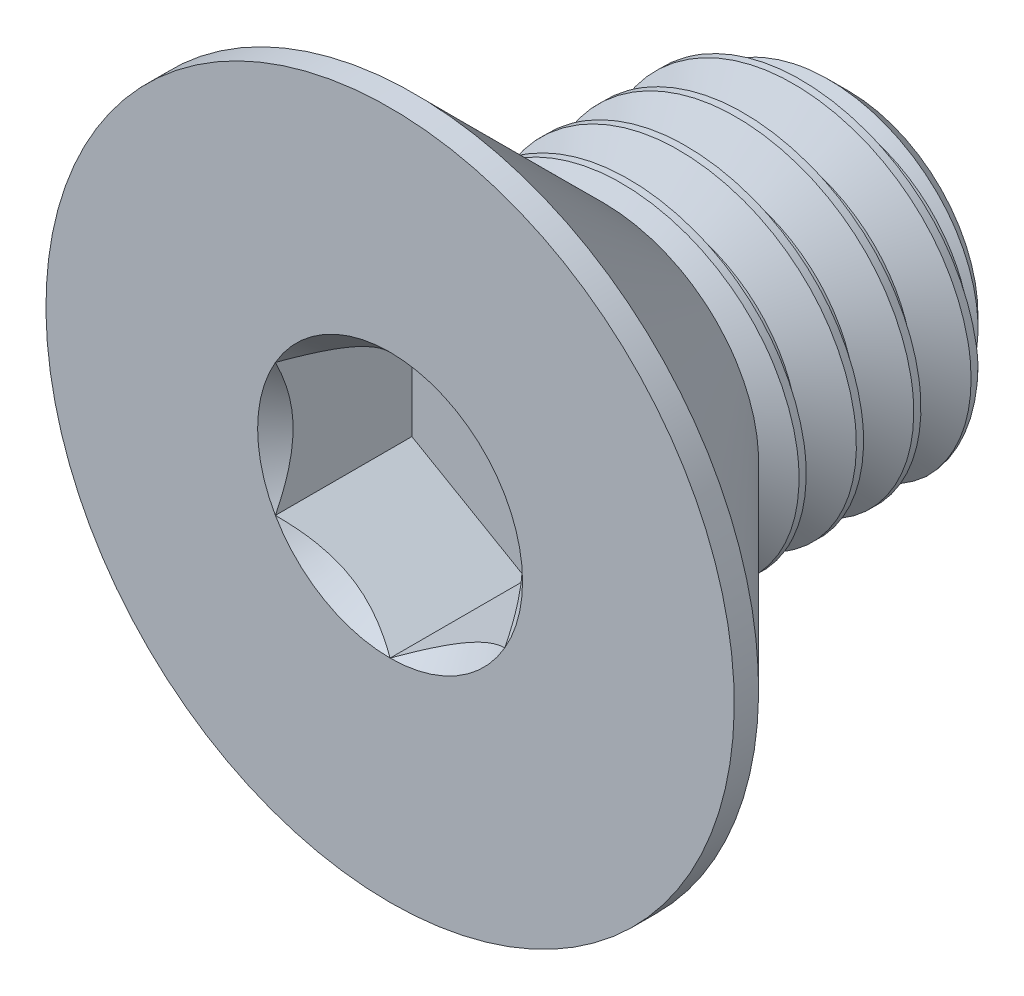
SolidWorks part; units mm, degrees
ref_plane "Front" through (0, 0, 0) normal (0, 0, 1) x (1, 0, 0)
ref_plane "Top" through (0, 0, 0) normal (0, 1, 0) x (1, 0, 0)
ref_plane "Right" through (0, 0, 0) normal (1, 0, 0) x (0, 0, -1)
sketch "Sketch1" plane through (0, 0, 0) normal (1, 0, 0) x (0, 0, -1)
  line L0 (0, 3) -> (0.2125, 3) construction
  line L1 (0.2125, 3) -> (1.7, 1.5125) construction
  line L2 (0, 1.5) -> (4, 1.5)
  line L3 (4, 1.5) -> (4, 0)
  line L4 (4, 0) -> (0, 0)
  line L5 (0, 0) -> (0, 3) construction
  line L6 (0, 3) -> (0, -3) construction
  line L7 (4, 1.5) -> (4, -1.5) construction
  line L8 (0, -3) -> (0.2125, -3) construction
  line L9 (0.2125, -3) -> (1.7, -1.5125) construction
  line L11 (0, 1.5) -> (0, 0)
  line L12 (1.7, 1.5125) -> (1.7, 0) construction
  line L13 (1.7, 1.5125) -> (1.4875, 1.5125) construction
  line L14 (1.4875, 1.5125) -> (1.275, 1.5125) construction
  line L15 (1.275, 1.5125) -> (1.0625, 1.5125) construction
  line L16 (1.0625, 1.5125) -> (0.85, 1.5125) construction
  line L17 (0.85, 1.5125) -> (0.6375, 1.5125) construction
  line L18 (0.6375, 1.5125) -> (0.425, 1.5125) construction
  line L19 (0.425, 1.5125) -> (0.2125, 1.5125) construction
  line L20 (0.2125, 1.5125) -> (0, 1.5125) construction
  line L21 (3.9688, 1.5541) -> (4.4688, 1.5541) construction
  line L22 (4.4688, 1.5541) -> (4.2188, 1.1211) construction
  line L23 (4.2188, 1.1211) -> (3.9688, 1.5541) construction
  line L24 (4.2188, 1.1211) -> (4.2188, 1.1752) construction
  line L25 (4, 1.5) -> (4.4375, 1.5) construction
  line L26 (4.1875, 1.1752) -> (4.25, 1.1752) construction
  line L27 (4.2188, 1.5) -> (4.2188, 1.5541) construction
  line L28 (3.9844, 1.5271) -> (4.4531, 1.5271) construction
  line L29 (1.7, 0) -> (1.7, -1.5125) construction
  point P31 (0.9562, -2.2562)
  point P33 (4.2188, 1.5271)
  point P36 (4.2188, 1.5271)
  point P38 (1.7, 1.5125)
  point P40 (0, 3)
  dimension "Head Dia" = 6
  dimension "Dia" = 3
  dimension "Head Ht" = 1.7
  dimension "Lg" = 4
  dimension "Head Angle" = 90
  dimension "Pitch" = 0.5
  dimension "D2" = 60
  dimension "D3" = 0.0625
  dimension "Thread Lg" = 2.3
revolve "Revolve1" add sketch "Sketch1" angle 360 mid plane about L4
sketch "Sketch 2" plane through (0, 0, 0) normal (0, 0, 1) x (1, 0, 0)
  line L0 (-3, 0) -> (3, 0) construction
  line L2 (0, 1.1547) -> (-1, 0.5774)
  line L3 (-1, 0.5774) -> (-1, -0.5774)
  line L4 (-1, -0.5774) -> (0, -1.1547)
  line L5 (0, -1.1547) -> (1, -0.5774)
  line L6 (1, -0.5774) -> (1, 0.5774)
  line L7 (1, 0.5774) -> (0, 1.1547)
  circle A1 centre (0, 0) radius 1.1547 construction
  circle A2 centre (0, 0) radius 1 construction
  point P2 (0, 0)
  point P8 (-1, -0.5774)
  point P16 (1, -0.5774)
  dimension "Hex" = 2
  dimension "Head OD (Tol)" = 6
sketch "Sketch3" plane through (0, 0, -4) normal (0, 0, -1) x (-1, 0, 0)
  circle A0 centre (0, 0) radius 1.5
sketch "Sketch2" plane through (0, 0, 0) normal (1, 0, 0) x (0, 0, -1)
  line L0 (4, -1.5) -> (4, 1.5) construction
  line L1 (4, -1.5) -> (4, 1.5) construction
  line L2 (3.9688, 1.5541) -> (4.2188, 1.1211) construction
  line L3 (4.2188, 1.1211) -> (4.4688, 1.5541) construction
  line L4 (4.4688, 1.5541) -> (3.9688, 1.5541) construction
  line L5 (4.2188, 1.1211) -> (4.2188, 1.1752) construction
  line L6 (4.2188, 1.5541) -> (4.2188, 1.5) construction
  line L7 (4, 1.5) -> (4.4375, 1.5) construction
  line L8 (4.1875, 1.1752) -> (4.25, 1.1752) construction
  line L9 (3.9942, 1.51) -> (4.4433, 1.51)
  line L10 (3.9844, 1.5271) -> (4.4531, 1.5271) construction
  line L11 (4.4433, 1.51) -> (4.25, 1.1752)
  line L12 (4.25, 1.1752) -> (4.1875, 1.1752)
  line L13 (4.1875, 1.1752) -> (3.9942, 1.51)
  point P12 (4.2188, 1.5)
  point P17 (4.2188, 1.5271)
  point P18 (4.2188, 1.1752)
  dimension "D1" = 0.0625
  dimension "D2" = 0.5
  dimension "D3" = 0.01
chamfer "Chamfer1" distance 0.375 angle 45 1 edges at (0, 1.5, -4)
sketch "Sketch7" plane through (0, 0, 0) normal (1, 0, 0) x (0, 0, -1)
  line L0 (0, 3) -> (0.2125, 3) construction
  line L1 (0.2125, 3) -> (1.7, 1.5125) construction
  line L2 (0, 3) -> (0.2125, 3)
  line L3 (0.2125, 3) -> (1.7, 1.5125)
  line L4 (1.7, 1.5125) -> (1.7, 0) construction
  line L5 (1.7, 1.5125) -> (1.7, 0)
  line L7 (0, 0) -> (0, 3) construction
  line L8 (0, 0) -> (0, 3)
  line L9 (0, 0) -> (1.7, 0)
  line L10 (16.5, 0) -> (-16.5, 0) construction
revolve "Revolve2" add sketch "Sketch7" angle 360 mid plane about L9
ref_plane "Plane1" through (0, 0, -1.7) normal (0, 0, 1) x (1, 0, 0)
sketch "Sketch8" plane through (0, 0, -1.7) normal (0, 0, 1) x (1, 0, 0)
  circle A0 centre (0, 0) radius 1.5125
extrude "Boss-Extrude1" add sketch "Sketch8" against normal through all draft 45
sketch "Sketch5" plane through (0, 0, 0) normal (0, 0, 1) x (1, 0, 0)
  line L1 (1, -0.5774) -> (1, 0.5774)
  line L2 (1, 0.5774) -> (0, 1.1547)
  line L3 (0, 1.1547) -> (-1, 0.5774)
  line L4 (-1, 0.5774) -> (-1, -0.5774)
  line L5 (-1, -0.5774) -> (0, -1.1547)
  line L6 (0, -1.1547) -> (1, -0.5774)
  circle A0 centre (0, 0) radius 1 construction
extrude "Cut-Extrude2" cut sketch "Sketch5" against normal blind 1.19
sketch "Sketch6" plane through (0, 0, 0) normal (0, 0, 1) x (1, 0, 0)
  circle A0 centre (0, 0) radius 1.1547
extrude "Cut-Extrude3" cut sketch "Sketch6" against normal blind 1.19 draft 45
sketch "Sketch10" plane through (0, 0, 0) normal (1, 0, 0) x (0, 0, -1)
  line L0 (4, 1.5) -> (4, -1.5) construction
  line L1 (0.2125, 3) -> (0.2125, -3) construction
  point P0 (3.25, -1.5)
  point P4 (0, 3)
  point P5 (0.2125, 3)
  point P7 (1.7125, 1.5)
  point P9 (4, 1.5)
  point P11 (4, -1.5)
  point P13 (0.2125, -3)
  dimension "D1" = 0.75
ref_plane "Contact Plane 1" through (0, 0, -1.7) normal (0, 0, 1) x (1, 0, 0)
ref_axis "Center Axis 1" through (0, 0, -4) along (0, 0, 1)
ref_plane "Plane2" through (0, 0, -1.7125) normal (0, 0, 1) x (1, 0, 0)
split "Split1" trim tools "Plane2" bodies to split 113 resulting bodies 121 122
curve "Helix/Spiral1" pitch 0.5 height 2.8 radius 1.5 centre (0, 0, -4) axis (0, 0, 1) start towards (0, 1, 0)
sweep "Cut-Sweep1" cut profiles "Sketch2" path "Helix/Spiral1" align with end faces yes
sketch "Sketch13" plane through (0, 0, 0) normal (1, 0, 0) x (0, 0, -1)
  line L0 (0.2125, 3) -> (0.3778, 2.8347) construction
  line L5 (4, 0) -> (0, 0) construction
  line L11 (2.0578, 1.1547) -> (2.0578, 0)
  line L12 (2.0578, 0) -> (1.2868, 0)
  line L13 (0.3778, 2.8347) -> (0.5431, 2.6694) construction
  line L14 (0.5431, 2.6694) -> (0.7083, 2.5042) construction
  line L15 (0.7083, 2.5042) -> (0.8736, 2.3389) construction
  line L16 (0.8736, 2.3389) -> (1.0389, 2.1736) construction
  line L17 (1.0389, 2.1736) -> (1.2042, 2.0083) construction
  line L18 (1.2042, 2.0083) -> (1.3694, 1.8431) construction
  line L19 (1.3694, 1.8431) -> (1.5347, 1.6778) construction
  line L20 (1.5347, 1.6778) -> (1.7, 1.5125) construction
  line L21 (2.0578, 1.1547) -> (1.2868, 1.9257)
  line L22 (1.2868, 1.9257) -> (1.2868, 0)
  point P20 (1.2868, 1.9257)
revolve "Revolve3" add sketch "Sketch13" angle 360 about L12
combine bodies "Combine1" operation type add bodies to combine 121 120
equation "\"D3@Helix/Spiral1\"=\"Thread Lg@Sketch1\" + (\"Pitch@Sketch1\"*1)"
equation "\"D1@Chamfer1\" = \"D4@Helix/Spiral1\" * .75"
equation "\"D1@Cut-Extrude2\" = \"Head Ht@Sketch1\" * .7"
equation "\"D1@Sketch10\" = \"D4@Helix/Spiral1\" * 1.5"
equation "\"D1@Cut-Extrude3\" = \"D1@Cut-Extrude2\""
equation "\"D2@Sketch2\"=\"D4@Helix/Spiral1\""
equation "\"D1@Sketch2\"=\"D2@Sketch2\"/8"
equation "\"D3@Sketch1\" = \"Pitch@Sketch1\" / 8"
equation "\"D4@Helix/Spiral1\" = \"Pitch@Sketch1\""
equation "\"Hex@Sketch5\"=\"Hex@Sketch 2\""
